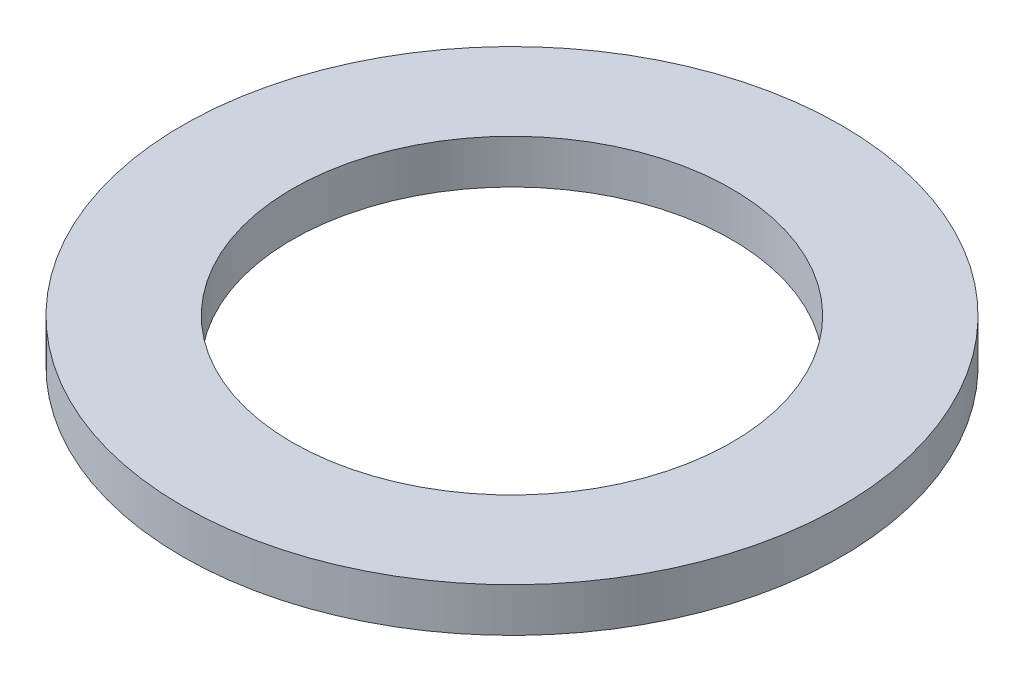
SolidWorks part; units mm, degrees
ref_plane "Front Plane" through (0, 0, 0) normal (0, 0, 1) x (1, 0, 0)
ref_plane "Top Plane" through (0, 0, 0) normal (0, 1, 0) x (1, 0, 0)
ref_plane "Right Plane" through (0, 0, 0) normal (1, 0, 0) x (0, 0, -1)
sketch "Sketch1" plane through (0, 0, 0) normal (0, 1, 0) x (1, 0, 0)
  circle A0 centre (0, 0) radius 52.5
  dimension "FLANGE_OD" = 105
extrude "Boss-Extrude1" add sketch "Sketch1" along normal blind 7
sketch "Sketch2" plane through (0, 0, 0) normal (0, 1, 0) x (1, 0, 0)
  circle A0 centre (0, 0) radius 35
  dimension "BORE_D" = 70
extrude "Cut-Extrude1" cut sketch "Sketch2" along normal through all
sketch "Sketch3" plane through (0, 7, 0) normal (0, 1, 0) x (1, 0, 0)
  circle A0 centre (0, 0) radius 20.6608 construction
  circle A1 centre (-20.6608, 0) radius 2.9466
  dimension "BOLT_D" = 5.8932
  dimension "BOLT_PCD" = 41.3216
extrude "Cut-Extrude2" cut sketch "Sketch3" against normal blind 4.7415 rebuild error yes
pattern_circular "CirPattern1" count 6 over 360 rebuild error yes
